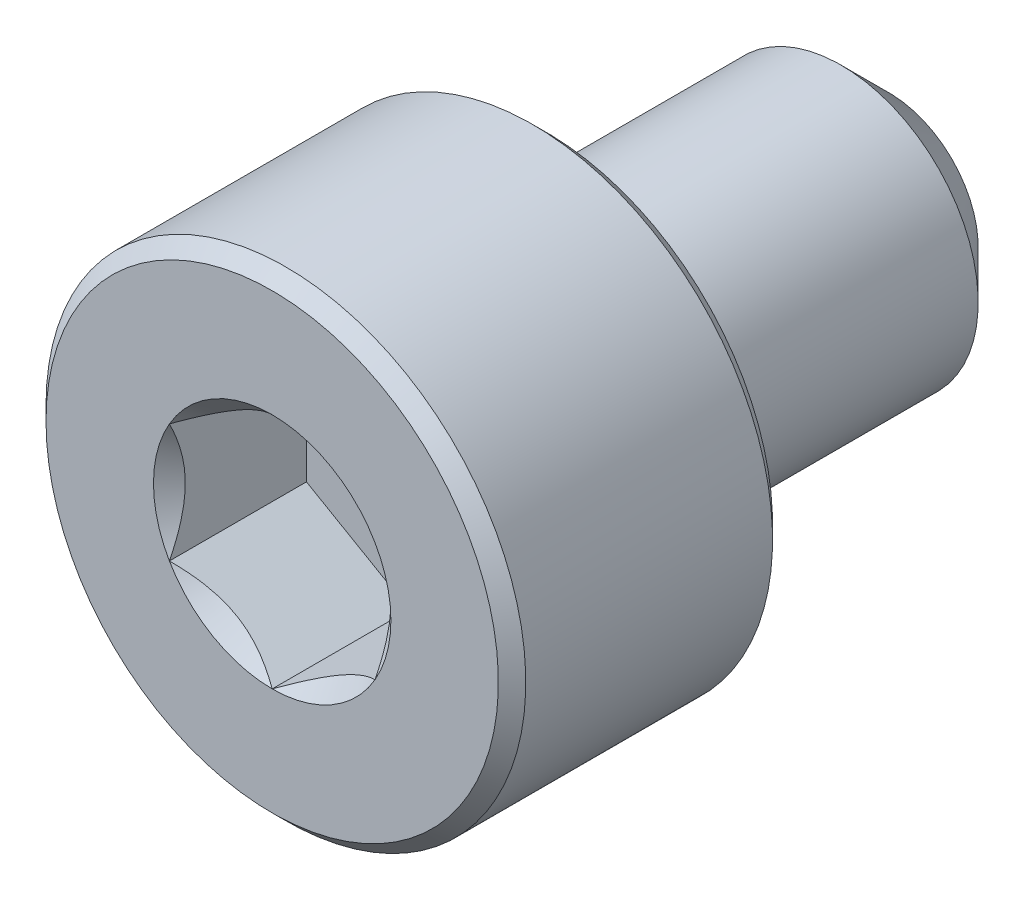
SolidWorks part; units mm, degrees
material "Alloy Steel"
ref_plane "Front Plane" through (0, 0, 0) normal (0, 0, 1) x (1, 0, 0)
ref_plane "Top Plane" through (0, 0, 0) normal (0, 1, 0) x (1, 0, 0)
ref_plane "Right Plane" through (0, 0, 0) normal (1, 0, 0) x (0, 0, -1)
sketch "Sketch1" plane through (0, 0, 0) normal (1, 0, 0) x (0, 0, -1)
  line L0 (-4.5, 0) -> (4.5, 0) construction
  line L1 (4.5, 0) -> (4.5, 1.3) construction
  line L2 (4.5, 1.3) -> (3.8, 2) construction
  line L3 (3.8, 2) -> (-0.5, 2) construction
  line L5 (-0.5, 2) -> (-0.5, 3.5) construction
  line L6 (-0.5, 3.5) -> (-4.5, 3.5) construction
  line L7 (-4.5, 3.5) -> (-4.5, 0) construction
  line L8 (4.5, 1.3) -> (4.5, 2) construction
  line L9 (4.4563, 2.0758) -> (4.8063, 1.4696) construction
  line L10 (4.8063, 1.4696) -> (5.1563, 2.0758) construction
  line L11 (5.1563, 2.0758) -> (4.4563, 2.0758) construction
  line L12 (4.8063, 2.0758) -> (4.8063, 2) construction
  line L13 (4.8063, 1.4696) -> (4.8063, 1.5453) construction
  line L14 (4.7625, 1.5453) -> (4.85, 1.5453) construction
  line L15 (4.5, 2) -> (5.1125, 2) construction
  line L16 (4.4781, 2.0379) -> (5.1344, 2.0379) construction
  line L17 (4.5, 0) -> (4.5, -2) construction
  line L18 (-0.7, 3.5) -> (-0.5, 3.3) construction
  line L19 (-4.3, 3.5) -> (-4.5, 3.3) construction
  point P0 (-4.5, 1.5)
  point P3 (2.05, 2)
  point P4 (0, 0)
  point P22 (4.8063, 1.5453)
  point P24 (-0.5, 2)
  point P25 (4.8063, 2)
  point P28 (4.8063, 2.0379)
  point P29 (2.05, -2)
  point P31 (-2.5, 3.5)
  point P37 (-1.2, 3.5)
  point P38 (-4.2, 3.5)
  point P41 (-2.5, 0)
  dimension "head height" = 4
  dimension "D1" = 45
  dimension "Head Diameter" = 7
  dimension "Thread Size" = 4
  dimension "drive size" = 3
  dimension "Thread Pitch" = 0.7
  dimension "D2" = 0.0875
  dimension "D3" = 0.7
  dimension "D4" = 2.45
  dimension "D7" = 0.2
  dimension "D8" = 0.2
  dimension "D9" = 0.2
  dimension "D10" = 0.1
  dimension "D11" = 0.5
  dimension "length" = 5
  dimension "Drive Depth" = 2
sketch "Sketch2" plane through (0, 0, 0) normal (1, 0, 0) x (0, 0, -1)
  line L1 (-4.3, 3.5) -> (-0.7, 3.5)
  line L4 (3.8, 2) -> (4.5, 1.3)
  line L5 (4.5, 1.3) -> (4.5, 0)
  line L6 (-0.7, 3.5) -> (-0.5, 3.3) construction
  line L7 (4.5, 0) -> (-4.5, 0)
  line L8 (-4.3, 3.5) -> (-4.5, 3.3) construction
  line L9 (-0.7, 3.5) -> (-0.5, 3.3)
  line L10 (-4.3, 3.5) -> (-4.5, 3.3)
  line L11 (-4.5, 3.3) -> (-4.5, 0)
  line L12 (-0.5, 3.3) -> (-0.5, 2)
  line L13 (-0.5, 2) -> (3.8, 2)
revolve "Revolve1" add sketch "Sketch2" angle 360 about L7
sketch "Sketch3" plane through (0, 0, 4.5) normal (0, 0, 1) x (1, 0, 0)
  line L1 (0, 1.7321) -> (-1.5, 0.866)
  line L2 (-1.5, 0.866) -> (-1.5, -0.866)
  line L3 (-1.5, -0.866) -> (0, -1.7321)
  line L4 (0, -1.7321) -> (1.5, -0.866)
  line L5 (1.5, -0.866) -> (1.5, 0.866)
  line L6 (1.5, 0.866) -> (0, 1.7321)
  circle A0 centre (0, 0) radius 1.5 construction
  dimension "D1" = 3
extrude "Cut-Extrude1" cut sketch "Sketch3" against normal up to vertex (2 mm away) up to point (0, 0, 2.5)
sketch "Sketch4" plane through (0, 0, 4.5) normal (0, 0, 1) x (1, 0, 0)
  circle A0 centre (0, 0) radius 1.7321
extrude "Cut-Extrude2" cut sketch "Sketch4" against normal blind 0.5 draft 45
ref_plane "Plane1" [suppressed] through (0, 0, 0.5) normal (0, 0, 1) x (1, 0, 0)
split "Split1" [suppressed] bodies to split 106
sketch "Sketch6" [suppressed] plane through (0, 0, -4.5) normal (0, 0, -1) x (-1, 0, 0)
  circle A0 centre (0, 0) radius 2
curve "Helix/Spiral1" [suppressed] pitch 0.7 height 5.7 turns 8.1429
sketch "Sketch7" [suppressed] plane through (0, 0, 0) normal (1, 0, 0) x (0, 0, -1)
  line L0 (4.4781, 2.0379) -> (5.1344, 2.0379)
  line L1 (5.1344, 2.0379) -> (4.85, 1.5453)
  line L2 (4.85, 1.5453) -> (4.7625, 1.5453)
  line L3 (4.7625, 1.5453) -> (4.4781, 2.0379)
sweep "Cut-Sweep1" [suppressed] cut profiles "Sketch7" path "Helix/Spiral1"
sketch "Sketch8" [suppressed] plane through (0, 0, 0.5) normal (0, 0, -1) x (-1, 0, 0)
  circle A0 centre (0, 0) radius 2
extrude "Boss-Extrude1" [suppressed] add sketch "Sketch8" along normal through all draft 45
ref_plane "Plane2" [suppressed] through (0, 0, 2.5) normal (0, 0, 1) x (1, 0, 0)
sketch "Sketch9" [suppressed] plane through (0, 0, 2.5) normal (0, 0, 1) x (1, 0, 0)
  line L0 (0, 3.4038) -> (0.0916, 3.4988)
  line L1 (0, 3.4038) -> (-0.0916, 3.4988)
  line L2 (0, 3.5) -> (0, 0) construction
  line L3 (-0.0916, 3.4988) -> (0, 0) construction
  line L4 (0, 0) -> (0.0916, 3.4988) construction
  arc A0 (0.0916, 3.4988) -> (-0.0916, 3.4988) centre (0, 0) ccw
  circle A1 centre (0, 0) radius 3.4038 construction
  dimension "D1" = 7
  dimension "D2" = 6.8075
  dimension "D3" = 3
extrude "Cut-Extrude4" [suppressed] cut sketch "Sketch9" against normal up to vertex and the other way up to vertex
pattern_circular "CirPattern2" [suppressed] count 96 over 360 about axis through (0, 0, 4.5) along (0, 0, -1) of bodies 113
equation "\"D2@Sketch1\" = \"Thread Pitch@Sketch1\" / 8"
equation "\"D3@Sketch1\" = \"Thread Pitch@Sketch1\""
equation "\"D3@Helix/Spiral1\" = \"length@Sketch1\" + \"Thread Pitch@Sketch1\""
equation "\"D4@Helix/Spiral1\" = \"Thread Pitch@Sketch1\""
equation "\"D4@Sketch1\" = \"Thread Pitch@Sketch1\" * 3.5"
equation "\"D7@Sketch1\"=\"head height@Sketch1\"*.05"
equation "\"D8@Sketch1\"=\"D7@Sketch1\""
equation "\"D9@Sketch1\"=\"D7@Sketch1\""
equation "\"D10@Sketch1\"=\"D7@Sketch1\"/2"
equation "\"D11@Sketch1\"=\"D10@Sketch1\"*5"
equation "\"D1@CirPattern2\"=( 360 / \"D3@Sketch9\" )*0.8"
equation "\"D1@Sketch3\" = \"drive size@Sketch1\""
equation "\"D2@Sketch9\"=\"Head Diameter@Sketch1\" * 0.9725"
